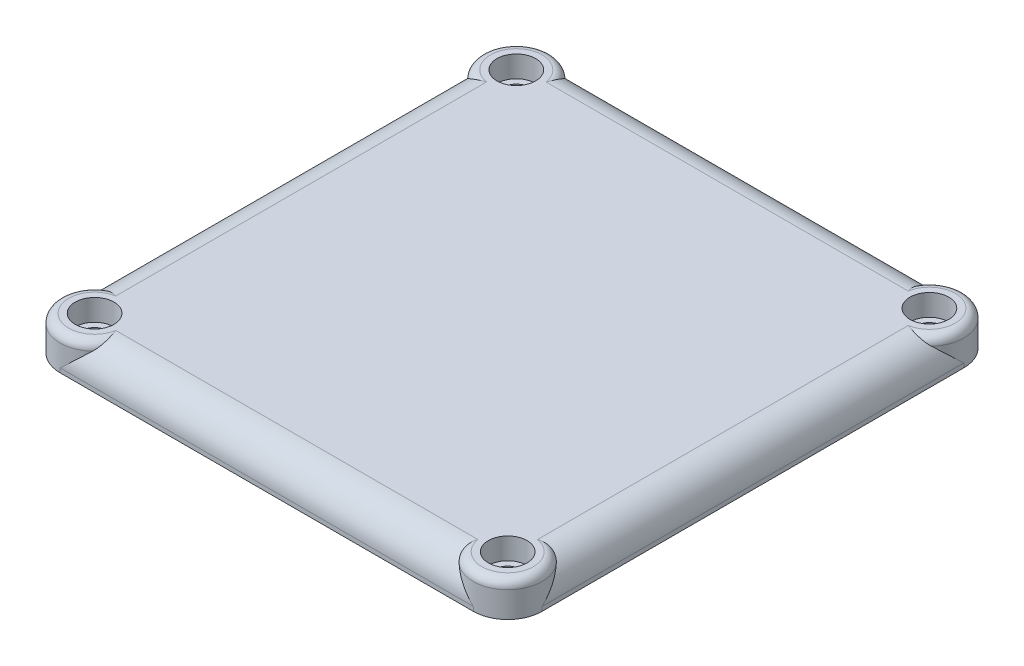
SolidWorks part; units mm, degrees
ref_plane "前视基准面" through (0, 0, 0) normal (0, 0, 1) x (1, 0, 0)
ref_plane "上视基准面" through (0, 0, 0) normal (0, 1, 0) x (1, 0, 0)
ref_plane "右视基准面" through (0, 0, 0) normal (1, 0, 0) x (0, 0, -1)
other "Configuration Table"
sketch "草图1" plane through (0, 0, 0) normal (0, 1, 0) x (1, 0, 0)
  line L1 (-48, 57) -> (48, 57)
  line L2 (-56, 49) -> (-56, -49)
  line L3 (-48, -57) -> (48, -57)
  line L4 (56, 49) -> (56, -49)
  line L5 (-56, 57) -> (56, -57) construction
  line L6 (-56, -57) -> (56, 57) construction
  arc A0 (48, 57) -> (56, 49) centre (48, 49) cw
  arc A1 (-56, -49) -> (-48, -57) centre (-48, -49) ccw
  arc A2 (-48, 57) -> (-56, 49) centre (-48, 49) ccw
  arc A3 (48, -57) -> (56, -49) centre (48, -49) ccw
  point P0 (0, 0)
  dimension "D3" = 8
  dimension "D1" = 114
  dimension "D2" = 112
extrude "凸台-拉伸1" add sketch "草图1" along normal blind 8
fillet "圆角1" radius 7 8 edges at (56, 8, 0) (53.6569, 8, 54.6569) (0, 8, 57) (-53.6569, 8, 54.6569) (-56, 8, 0) (-53.6569, 8, -54.6569) (0, 8, -57) (53.6569, 8, -54.6569)
sketch "草图2" plane through (0, 0, 0) normal (0, 1, 0) x (1, 0, 0)
  circle A0 centre (48, 49) radius 8
  arc A1 (56, 49) -> (48, 57) centre (48, 49) ccw construction
extrude "凸台-拉伸2" add sketch "草图2" along normal blind 8
mirror "镜向1" about plane through (0, 0, 0) normal (0, 0, 1) of "凸台-拉伸2"
mirror "镜向2" about plane through (0, 0, 0) normal (1, 0, 0) of "镜向1"
fillet "圆角2" radius 2 4 edges at (53.6569, 8, -54.6569) (-53.6569, 8, -54.6569) (-53.6569, 8, 54.6569) (53.6569, 8, 54.6569)
sketch "草图3" plane through (0, 0, 0) normal (0, -1, 0) x (1, 0, 0)
  line L0 (0, 57) -> (0, 0) construction
  line L1 (-48, 57) -> (48, 57) construction
  line L2 (0, 0) -> (56, 0) construction
  line L3 (56, 49) -> (56, -49) construction
  line L4 (48, -57) -> (-48, -57) construction
  line L5 (-49, 50) -> (49, 50)
  line L6 (-49, 50) -> (-49, -50)
  line L7 (-49, -50) -> (49, -50)
  line L8 (49, 50) -> (49, -50)
  line L9 (-49, 50) -> (49, -50) construction
  line L10 (-49, -50) -> (49, 50) construction
  circle A0 centre (48, 49) radius 8
  arc A1 (56, 49) -> (48, 57) centre (48, 49) ccw construction
  circle A2 centre (-48, 49) radius 8
  circle A3 centre (-48, -49) radius 8
  circle A4 centre (48, -49) radius 8
  dimension "D1" = 7
  dimension "D2" = 7
extrude "切除-拉伸1" cut sketch "草图3" against normal blind 3 contours L7 A4 L8 A0 L5 A2 L6 A3 region at (0, 0, 0)
sketch "草图4" plane through (0, 8, 0) normal (0, 1, 0) x (1, 0, 0)
  point P0 (-48, 49)
  point P3 (48, 49)
  point P6 (48, -49)
  point P9 (-48, -49)
hole_wizard "M6 六角头螺栓的柱形沉头孔1" positions "草图4" profile "草图5" counterbore size "M6" standard "GB"
sketch "草图5" plane through (-48, 8, -49) normal (1, 0, 0) x (0, 0, 1)
  line L0 (0, 0) -> (0, 14.2026)
  line L1 (0, 14.2026) -> (3, 12.4)
  line L2 (3, 12.4) -> (3, 5)
  line L3 (3, 5) -> (4.5, 5)
  line L4 (4.5, 5) -> (4.5, 0)
  line L5 (4.5, 0) -> (0, 0)
  line L10 (0, 14.2026) -> (-3, 12.4) construction
  line L11 (0, -6.35) -> (0, 107.95) construction
  dimension "孔直径" = 6
  dimension "孔深度" = 12.4
  dimension "柱形沉头孔直径" = 9
  dimension "柱形沉头孔深度" = 5
  dimension "导头角度" = 118
fillet "圆角3" radius 2 8 edges at (-40.0627, 1.5, -50) (-49, 1.5, -41.0627) (-49, 1.5, 41.0627) (-40.0627, 1.5, 50) (40.0627, 1.5, -50) (49, 1.5, -41.0627) (40.0627, 1.5, 50) (49, 1.5, 41.0627)
